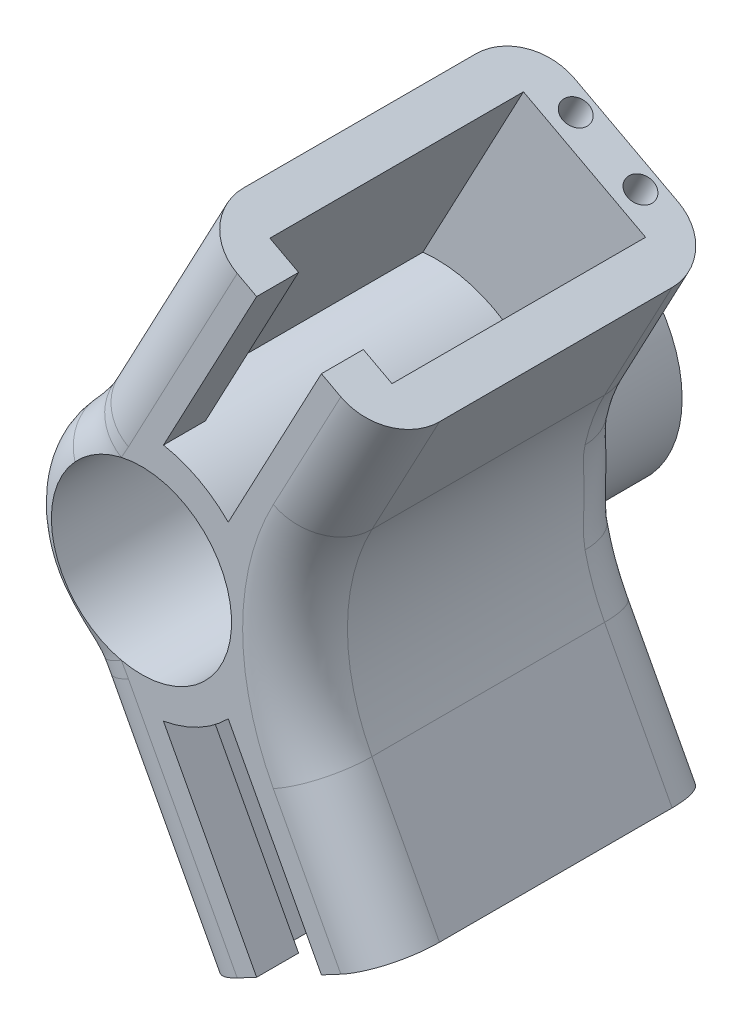
SolidWorks part; units mm, degrees
material "PETG"
ref_plane "Front Plane" through (0, 0, 0) normal (0, 0, 1) x (1, 0, 0)
ref_plane "Top Plane" through (0, 0, 0) normal (0, 1, 0) x (1, 0, 0)
ref_plane "Right Plane" through (0, 0, 0) normal (1, 0, 0) x (0, 0, -1)
sketch "Sketch2" plane through (0, 0, 0) normal (0, 0, 1) x (1, 0, 0)
  circle A0 centre (0, 0) radius 8.6
  circle A1 centre (0, 0) radius 11.6
  dimension "D1" = 17.2
  dimension "D2" = 3
extrude "Boss-Extrude1" add sketch "Sketch2" along normal mid plane 40
sketch "Sketch3" plane through (0, 0, 0) normal (0, 0, 1) x (1, 0, 0)
  line L0 (0, -15.9069) -> (0, 32.1514) construction
  line L1 (-21.7632, 0) -> (52.0967, 0) construction
  line L2 (0, 0) -> (39.7652, 21.1435) construction
  dimension "D1" = 28
ref_axis "Axis1" through (0, 0, 20) along (0, 0, -1)
ref_plane "Plane1" through (0, 0, 0) normal (0.4695, 0.8829, 0) x (0, 0, -1)
sketch "Sketch4" plane through (0, 0, 0) normal (0.4695, 0.8829, 0) x (0, 0, -1)
  line L0 (-20, 10.6) -> (12.2, 10.6)
  line L1 (-16, -6.6) -> (8.2, -6.6)
  line L2 (-16, -6.6) -> (-16, 6.6)
  line L3 (-16, 6.6) -> (8.2, 6.6)
  line L4 (8.2, -6.6) -> (8.2, 6.6)
  line L5 (-16, -6.6) -> (8.2, 6.6) construction
  line L6 (-16, 6.6) -> (8.2, -6.6) construction
  line L7 (12.2, -10.6) -> (12.2, 10.6)
  line L8 (-20, -10.6) -> (12.2, -10.6)
  line L9 (-20, -10.6) -> (-20, 10.6)
  line L10 (-20, 11.6) -> (-20, -11.6) construction
  line L11 (-20, 11.6) -> (-20, -11.6) construction
  line L12 (-20, 3.5) -> (-16, 3.5)
  line L13 (-20, -3.5) -> (-16, -3.5)
  line L14 (-20, 0) -> (20, 0) construction
  point P0 (-3.9, 0)
  point P16 (-20, 0)
  dimension "D1" = 24.2
  dimension "D2" = 13.2
  dimension "D4" = 7
  dimension "D5" = 3.5
  dimension "D3" = 4
extrude "Boss-Extrude2" add sketch "Sketch4" against normal up to surface (20.4606 mm away) from offset 30 contours L13 L9 L8 L7 L0 L12 L2 L3 L4 L1 region at (-9.0188, 4.7954, 3.9) up to face at (11.6, 0, 20)
sketch "Sketch5" plane through (14.0841, 26.4884, 0) normal (0.4695, 0.8829, 0) x (0.8829, -0.4695, 0)
  line L0 (6.6, 8.2) -> (-6.6, 8.2) construction
  line L1 (6.6, 8.2) -> (-6.6, 8.2)
  line L2 (-10.6, 10.45) -> (10.6, 10.45) construction
  line L3 (-10.6, -20) -> (-10.6, 12.2) construction
  line L4 (10.6, -20) -> (10.6, 12.2) construction
  line L5 (0, 8.2) -> (0, 11.8034) construction
  circle A0 centre (-3.5, 10.45) radius 1.25
  circle A1 centre (3.5, 10.45) radius 1.25
  dimension "D3" = 2.5
  dimension "D1" = 2.25
  dimension "D2" = 7
  dimension "D4" = 3.5
extrude "Cut-Extrude1" cut sketch "Sketch5" against normal blind 10 contours A0 | A1 region at (10.9938, 28.1316, -10.45) region at (17.1745, 24.8453, -10.45)
mirror "Mirror3" about plane through (0, 0, 0) normal (0, 1, 0) of "Cut-Extrude1", "Boss-Extrude2"
fillet "Fillet1" radius 20 3 edges at (-7.1472, -9.1366, 3.9) (-7.1472, 9.1366, 3.9) (12.0052, 0, 3.9)
fillet "Fillet2" radius 5 14 edges at (-6.978, 9.7932, -12.2) (20.2205, 15.4507, -12.2) (20.2205, -15.4507, -12.2) (-0.4659, -21.7024, 20) (-6.978, -9.7932, 20) (-6.978, 9.7932, 20) (20.2205, -15.4507, 20) (14.6566, 0, 20) (-0.4659, 21.7024, -12.2) (-6.978, -9.7932, -12.2) (-0.4659, -21.7024, -12.2) (14.6566, 0, -12.2) (-0.4659, 21.7024, 20) (20.2205, 15.4507, 20)
equation "\"DTailTube\"= 16mm'Диаметр трубки хвостового оперения"
equation "\"FusLenght\"= 700mm"
equation "\"DMotor\"= 35.2mm"
equation "\"MotorArm\"= 320mm"
equation "\"DFus\"= 150mm"
equation "\"DFusTube\"= 30mm'Диаметр трубки внутри фюзеляжа"
equation "\"FusTubeHeight\"= 40mm"
equation "\"FusCentralPartLenght\"= 410mm"
equation "\"FusNoseLenght\"= 150mm"
equation "\"WingOffset\"= 1mm'Расстояние от внутренней поверхности фюзеляжа до профиля крыла по вертикали"
equation "\"EllipseRatio\"= 0.95'Центральная часть фюзеляжа - эллипс. Этот параметр - отношение длин осей эллипса"
equation "\"FrameOffset\"= 0.6mm"
equation "\"DThreadedInsert\"= 3mm'Внешний диамер резьбовых втулок"
equation "\"ThreadedInsertLenght\"=4mm'Длина резьбовых втулок"
equation "\"ThreadedInsertThread\"=2mm'Диаметр резьбы втулки"
equation "\"CenterSectionLenght\"= 140mm'Длина центроплана"
equation "\"b\"= 1700mm'Размах"
equation "\"cwr\"= 236mm'Корневая хорда крыла"
equation "\"TR\"= 0.75'Сужение крыла"
equation "\"cwt\"= \"TR\" * \"cwr\"'Концевая хорда крыла"
equation "\"DWingMainSpar\"= 16mm'Диаметр главного лонжерона крыла"
equation "\"DWingSecondSpar\"= 8mm'Диаметр второго лонжерона крыла"
equation "\"WingSparsDistance\"= 80mm'Расстояния между отверстиями по лонжерон крыла"
equation "\"c\"= 210mm'САХ крыла"
equation "\"FusTubeLenght\"= \"FusLenght\"-90mm'Длина трубки фюзеляжа"
equation "\"bt\"=291mm'Высота лопатки хвоста"
equation "\"ct\"=182mm'Корневая хорда хвоста"
equation "\"lambda_t\"=0.3'Доля хвоста, занатая рулем высоты"
equation "\"TailTubeLenght\"=680mm'Длина хвостовой балки"
equation "\"DStringer\"=6mm'Диаметр стрингеров"
equation "\"TailConnectorBaseLenght\"=20mm'Высота основания конектора хвоста"
equation "\"CargoHolderHoleDistance\"=30mm'Расстояние между крепежными отверстиями для держателя груза"
equation "\"FuselageThickness\"=1.2mm'Толщина фюзеляжа"
equation "\"DTailSpar\"=6mm'Диаметр лонжерона хвостового оперения"
equation "\"TailSparDistance\"=40mm'Расстояние между лонжеронами хвостового оперения"
equation "\"CrossSectionWidth\"=15mm'Ширина кольцевой части шпангоута"
equation "\"HingeLenght\"=30mm'Длина отверстия под шарнир хвостового оперения"
equation "\"HingeWidth\"=2.4mm'Высота отверстия под шарнир ХО"
equation "\"HingeDepth\"=15mm'Глубина отверстия под шарнир ХО"
equation "\"D1@Sketch2\"=\"DTailTube\"+1.2"
equation "\"D1@Sketch4\"=23+1.2"
equation "\"D2@Sketch4\"=12+1.2"
equation "\"D19@Boss-Extrude2\"=\"DTailTube\"/2 + 22"
equation "\"D5@Sketch4\"=\"D4@Sketch4\"/2"
equation "\"D4@Sketch5\"=\"D2@Sketch5\"/2"
